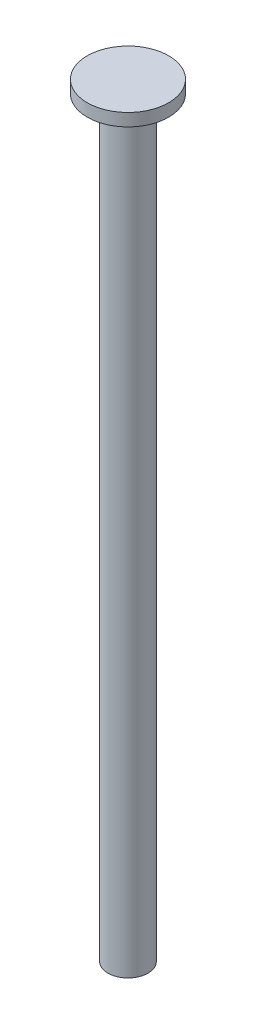
SolidWorks part; units mm, degrees
ref_plane "Front Plane" through (0, 0, 0) normal (0, 0, 1) x (1, 0, 0)
ref_plane "Top Plane" through (0, 0, 0) normal (0, 1, 0) x (1, 0, 0)
ref_plane "Right Plane" through (0, 0, 0) normal (1, 0, 0) x (0, 0, -1)
sketch "Sketch1" plane through (0, 0, 0) normal (0, 1, 0) x (1, 0, 0)
  circle A0 centre (0, 0) radius 3.25
  dimension "D1" = 6.5
extrude "Boss-Extrude1" add sketch "Sketch1" along normal blind 1 contours A0
sketch "Sketch2" plane through (0, 0, 0) normal (0, 1, 0) x (1, 0, 0)
  circle A0 centre (0, 0) radius 1.6
  dimension "D1" = 3.2
extrude "Boss-Extrude2" add sketch "Sketch2" against normal blind 60
